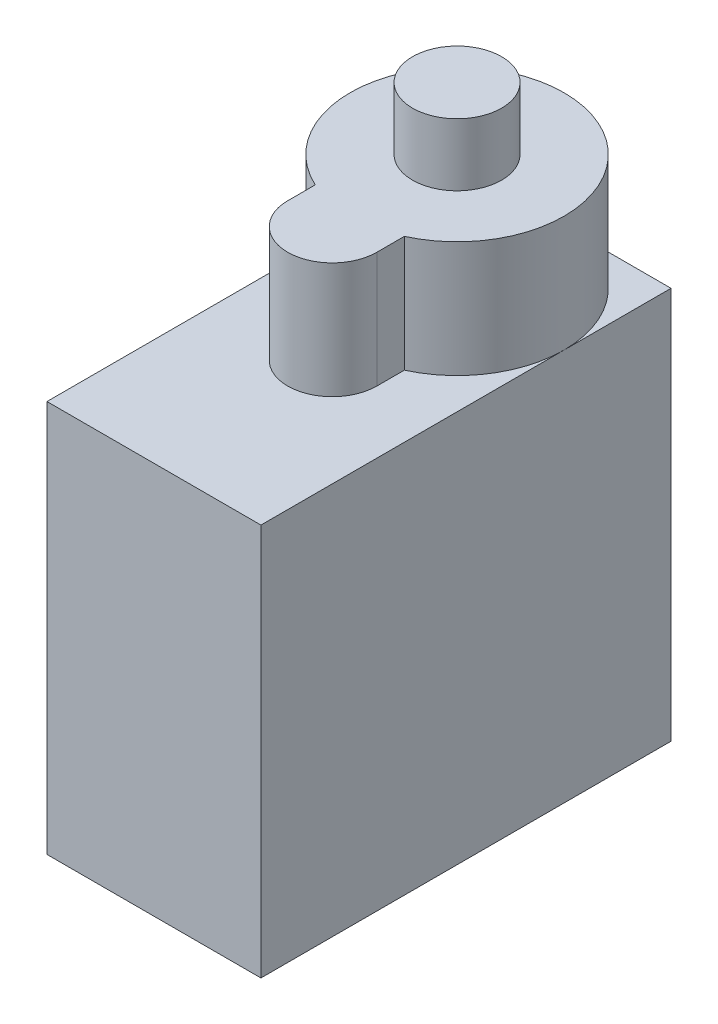
SolidWorks part; units mm, degrees
ref_plane "Front Plane" through (0, 0, 0) normal (0, 0, 1) x (1, 0, 0)
ref_plane "Top Plane" through (0, 0, 0) normal (0, 1, 0) x (1, 0, 0)
ref_plane "Right Plane" through (0, 0, 0) normal (1, 0, 0) x (0, 0, -1)
sketch "Sketch1" plane through (0, 0, 0) normal (0, 1, 0) x (1, 0, 0)
  line L1 (45.3144, -93.1516) -> (57.3144, -93.1516)
  line L2 (45.3144, -93.1516) -> (45.3144, -116.1516)
  line L3 (45.3144, -116.1516) -> (57.3144, -116.1516)
  line L4 (57.3144, -93.1516) -> (57.3144, -116.1516)
  point P4 (0, 0)
  dimension "D1" = 23
  dimension "D2" = 12
sketch "Sketch3" plane through (0, 0, 0) normal (0, 1, 0) x (1, 0, 0)
  line L0 (45.3144, -93.1516) -> (57.3144, -93.1516) construction
  line L1 (57.3144, -93.1516) -> (57.3144, -116.1516) construction
  line L2 (45.3144, -93.1516) -> (45.3144, -116.1516) construction
  line L5 (48.8144, -106.1516) -> (48.8144, -104.606)
  line L6 (53.8144, -104.606) -> (53.8144, -106.1516)
  arc A0 (53.8144, -104.606) -> (48.8144, -104.606) centre (51.3144, -99.1516) ccw
  arc A1 (48.8144, -106.1516) -> (53.8144, -106.1516) centre (51.3144, -106.1516) ccw
  dimension "D1" = 12
  dimension "D4" = 5
  dimension "D2" = 6
  dimension "D3" = 6
  dimension "D5" = 6
  dimension "D6" = 13
sketch "Sketch4" plane through (0, 0, 0) normal (0, 1, 0) x (1, 0, 0)
  line L0 (57.3144, -93.1516) -> (57.3144, -116.1516) construction
  line L1 (45.3144, -93.1516) -> (57.3144, -93.1516) construction
  circle A0 centre (51.3144, -99.1516) radius 2.5
  point P4 (0, 0)
  point P6 (46.8141, -104.9972)
  dimension "D3" = 5
  dimension "D1" = 6
  dimension "D2" = 6
extrude "Boss-Extrude2" add sketch "Sketch4" along normal blind 32
extrude "Boss-Extrude3" add sketch "Sketch3" along normal blind 28.5
extrude "Boss-Extrude4" add sketch "Sketch1" along normal blind 22
sketch "Sketch5" plane through (0, 0, 0) normal (0, 1, 0) x (1, 0, 0)
  line L0 (57.3144, -116.1516) -> (57.3144, -93.1516) construction
  line L1 (57.3144, -93.1516) -> (45.3144, -93.1516) construction
  line L3 (48.8144, -106.1516) -> (48.8144, -104.606)
  line L4 (53.8144, -106.1516) -> (53.8144, -104.606)
  arc A0 (48.8144, -106.1516) -> (53.8144, -106.1516) centre (51.3144, -106.1516) ccw
  circle A1 centre (51.3144, -99.1516) radius 6 construction
  arc A2 (48.8144, -104.606) -> (53.8144, -104.606) centre (51.3144, -99.1516) ccw
  dimension "D1" = 5
  dimension "D2" = 6
  dimension "D3" = 13
